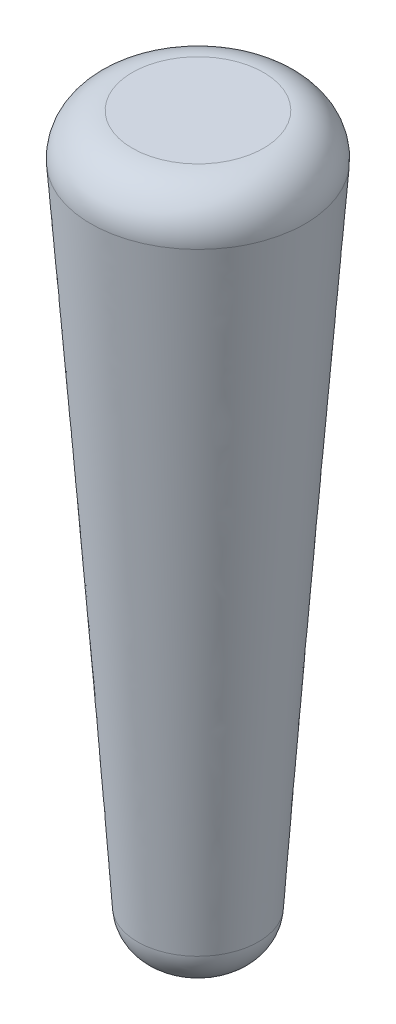
SolidWorks part; units mm, degrees
ref_plane "Front" through (0, 0, 0) normal (0, 0, 1) x (1, 0, 0)
ref_plane "Top" through (0, 0, 0) normal (0, 1, 0) x (1, 0, 0)
ref_plane "Right" through (0, 0, 0) normal (1, 0, 0) x (0, 0, -1)
sketch "Sketch1" plane through (0, 0, 0) normal (0, 1, 0) x (1, 0, 0)
  circle A0 centre (0, 0) radius 67.5
  dimension "D1" = 135
ref_plane "Plane2" through (0, -445.008, 0) normal (0, 1, 0) x (-1, 0, 0)
sketch "Sketch2" plane through (0, -445.008, 0) normal (0, 1, 0) x (-1, 0, 0)
  circle A0 centre (0, 0) radius 35.3901
  dimension "D1" = 70.7803
loft "Loft1" add profiles "Sketch1", "Sketch2" connector at (-66.0191, 0, -14.0617) connector at (-30.5069, -445.008, -17.9384)
fillet "Fillet3" radius 25.4 2 edges at (0, 0, 67.5) (0, -445.008, 35.3901)
sketch "Sketch3" plane through (0, -445.008, 0) normal (0, -1, 0) x (1, 0, 0)
  circle A0 centre (0, 0) radius 36.9354 construction
  point P0 (0, 0)
